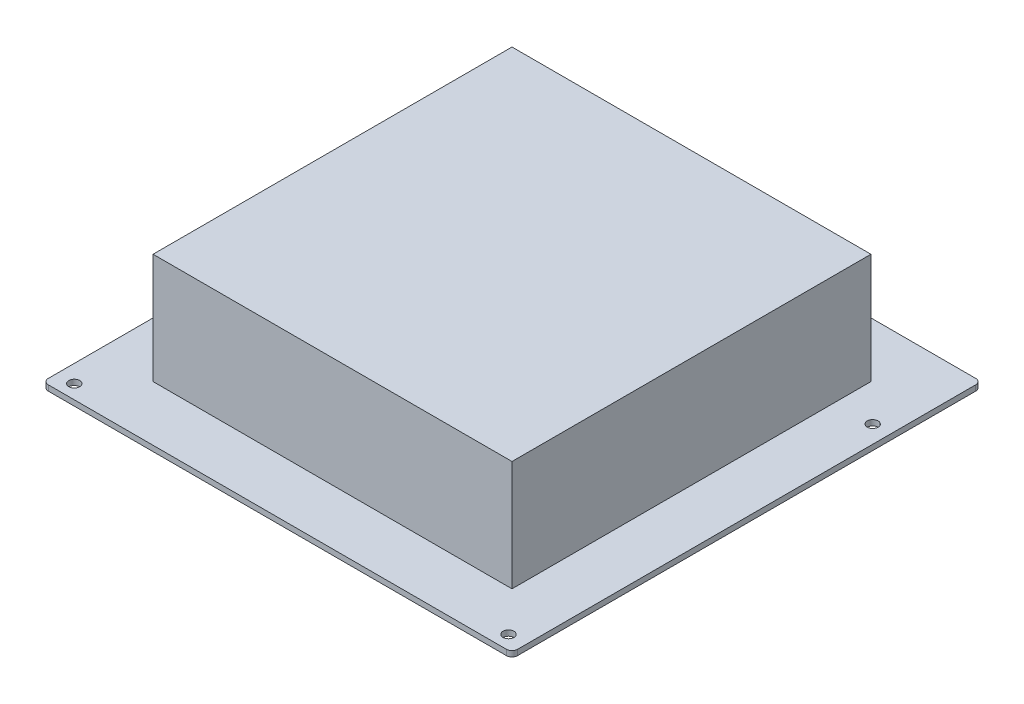
SolidWorks part; units mm, degrees
ref_plane "Front Plane" through (0, 0, 0) normal (0, 0, 1) x (1, 0, 0)
ref_plane "Top Plane" through (0, 0, 0) normal (0, 1, 0) x (1, 0, 0)
ref_plane "Right Plane" through (0, 0, 0) normal (1, 0, 0) x (0, 0, -1)
sketch "Sketch1" plane through (0, 0, 0) normal (0, 1, 0) x (1, 0, 0)
  line L1 (-85.09, -85.09) -> (85.09, -85.09)
  line L2 (-85.09, -85.09) -> (-85.09, 85.09)
  line L3 (-85.09, 85.09) -> (85.09, 85.09)
  line L4 (85.09, -85.09) -> (85.09, 85.09)
  line L5 (-85.09, -85.09) -> (85.09, 85.09) construction
  line L6 (-85.09, 85.09) -> (85.09, -85.09) construction
  point P0 (0, 0)
  dimension "D1" = 170.18
  dimension "D2" = 170.18
extrude "Boss-Extrude1" add sketch "Sketch1" along normal blind 2
fillet "Fillet1" radius 2 4 edges at (-85.09, 1, -85.09) (85.09, 1, -85.09) (85.09, 1, 85.09) (-85.09, 1, 85.09)
sketch "Sketch2" plane through (0, 0, 0) normal (0, 1, 0) x (1, 0, 0)
  line L0 (-85.09, 83.09) -> (-85.09, -83.09) construction
  line L1 (-83.09, -85.09) -> (83.09, -85.09) construction
  point P0 (-78.74, -80.01)
  point P1 (78.74, -80.01)
  point P2 (78.74, 52.07)
  point P3 (-78.74, 71.3216)
  dimension "D1" = 6.35
  dimension "D2" = 5.08
  dimension "D3" = 157.48
  dimension "D4" = 132.08
sketch "Sketch3" plane through (0, 2, 0) normal (0, 1, 0) x (1, 0, 0)
  circle A0 centre (-78.74, 71.3216) radius 1.975
  circle A1 centre (78.74, 52.07) radius 1.975
  circle A2 centre (78.74, -80.01) radius 1.975
  circle A3 centre (-78.74, -80.01) radius 1.975
  dimension "D1" = 3.95
extrude "Cut-Extrude1" cut sketch "Sketch3" against normal through all
sketch "Sketch4" plane through (0, 2, 0) normal (0, 1, 0) x (1, 0, 0)
  line L0 (-85.09, 83.09) -> (-85.09, -83.09) construction
  line L1 (-65.09, -65.09) -> (65.09, -65.09)
  line L2 (-65.09, -65.09) -> (-65.09, 65.09)
  line L3 (-65.09, 65.09) -> (65.09, 65.09)
  line L4 (65.09, -65.09) -> (65.09, 65.09)
  line L5 (-83.09, -85.09) -> (83.09, -85.09) construction
  line L6 (85.09, -83.09) -> (85.09, 83.09) construction
  line L7 (83.09, 85.09) -> (-83.09, 85.09) construction
  dimension "D1" = 20
  dimension "D2" = 20
  dimension "D3" = 20
  dimension "D4" = 20
extrude "Boss-Extrude2" add sketch "Sketch4" along normal blind 40
